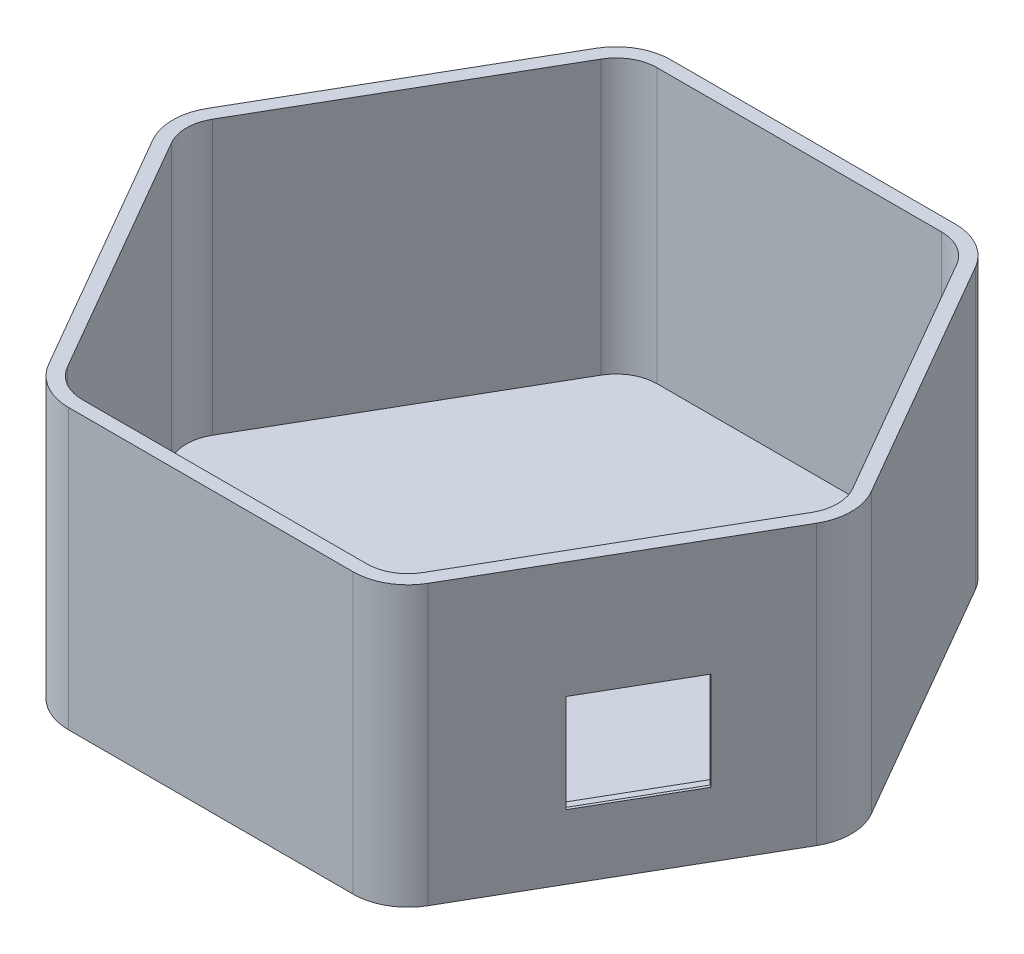
SolidWorks part; units mm, degrees
ref_plane "Front" through (0, 0, 0) normal (0, 0, 1) x (1, 0, 0)
ref_plane "Top" through (0, 0, 0) normal (0, 1, 0) x (1, 0, 0)
ref_plane "Right" through (0, 0, 0) normal (1, 0, 0) x (0, 0, -1)
sketch "Croquis1" plane through (0, 0, 0) normal (0, 1, 0) x (1, 0, 0)
  line L1 (-121.2436, -10) -> (-69.282, -100)
  line L2 (-51.9615, -110) -> (51.9615, -110)
  line L3 (69.282, -100) -> (121.2436, -10)
  line L4 (121.2436, 10) -> (69.282, 100)
  line L5 (51.9615, 110) -> (-51.9615, 110)
  line L6 (-69.282, 100) -> (-121.2436, 10)
  circle A0 centre (0, 0) radius 110 construction
  arc A1 (-69.282, 100) -> (-51.9615, 110) centre (-51.9615, 90) cw
  arc A2 (69.282, 100) -> (51.9615, 110) centre (51.9615, 90) ccw
  arc A3 (121.2436, -10) -> (121.2436, 10) centre (103.923, 0) ccw
  arc A4 (51.9615, -110) -> (69.282, -100) centre (51.9615, -90) ccw
  arc A5 (-69.282, -100) -> (-51.9615, -110) centre (-51.9615, -90) ccw
  arc A6 (-121.2436, -10) -> (-121.2436, 10) centre (-103.923, 0) cw
  dimension "D1" = 220
  dimension "D2" = 20
extrude "Saliente-Extruir1" add sketch "Croquis1" along normal blind 2
sketch "Croquis2" plane through (0, 2, 0) normal (0, 1, 0) x (1, 0, 0)
  line L6 (-64.9519, 97.5) -> (-116.9134, 7.5)
  line L7 (-116.9134, -7.5) -> (-64.9519, -97.5)
  line L8 (-51.9615, -105) -> (51.9615, -105)
  line L9 (64.9519, -97.5) -> (116.9134, -7.5)
  line L10 (116.9134, 7.5) -> (64.9519, 97.5)
  line L11 (51.9615, 105) -> (-51.9615, 105)
  line L12 (-69.282, 100) -> (-121.2436, 10)
  line L13 (-121.2436, -10) -> (-69.282, -100)
  line L14 (-51.9615, -110) -> (51.9615, -110)
  line L15 (69.282, -100) -> (121.2436, -10)
  line L16 (121.2436, 10) -> (69.282, 100)
  line L17 (51.9615, 110) -> (-51.9615, 110)
  line L18 (-69.282, 100) -> (-121.2436, 10)
  line L19 (-121.2436, -10) -> (-69.282, -100)
  line L20 (-51.9615, -110) -> (51.9615, -110)
  line L21 (69.282, -100) -> (121.2436, -10)
  line L22 (121.2436, 10) -> (69.282, 100)
  line L23 (51.9615, 110) -> (-51.9615, 110)
  arc A6 (-116.9134, 7.5) -> (-116.9134, -7.5) centre (-103.923, 0) ccw
  arc A7 (-64.9519, -97.5) -> (-51.9615, -105) centre (-51.9615, -90) ccw
  arc A8 (51.9615, -105) -> (64.9519, -97.5) centre (51.9615, -90) ccw
  arc A9 (116.9134, -7.5) -> (116.9134, 7.5) centre (103.923, 0) ccw
  arc A10 (64.9519, 97.5) -> (51.9615, 105) centre (51.9615, 90) ccw
  arc A11 (-51.9615, 105) -> (-64.9519, 97.5) centre (-51.9615, 90) ccw
  arc A12 (-51.9615, 110) -> (-69.282, 100) centre (-51.9615, 90) ccw
  arc A13 (-121.2436, 10) -> (-121.2436, -10) centre (-103.923, 0) ccw
  arc A14 (-69.282, -100) -> (-51.9615, -110) centre (-51.9615, -90) ccw
  arc A15 (51.9615, -110) -> (69.282, -100) centre (51.9615, -90) ccw
  arc A16 (121.2436, -10) -> (121.2436, 10) centre (103.923, 0) ccw
  arc A17 (69.282, 100) -> (51.9615, 110) centre (51.9615, 90) ccw
  arc A18 (-51.9615, 110) -> (-69.282, 100) centre (-51.9615, 90) ccw
  arc A19 (-121.2436, 10) -> (-121.2436, -10) centre (-103.923, 0) ccw
  arc A20 (-69.282, -100) -> (-51.9615, -110) centre (-51.9615, -90) ccw
  arc A21 (51.9615, -110) -> (69.282, -100) centre (51.9615, -90) ccw
  arc A22 (121.2436, -10) -> (121.2436, 10) centre (103.923, 0) ccw
  arc A23 (69.282, 100) -> (51.9615, 110) centre (51.9615, 90) ccw
  dimension "D1" = 0
  dimension "D2" = 5
extrude "Saliente-Extruir2" add sketch "Croquis2" along normal blind 100
sketch "Croquis3" plane through (90.9327, 0, 52.5) normal (-0.866, 0, -0.5) x (-0.5, 0, 0.866)
  line L1 (27.9238, 60.6352) -> (27.9238, 22.4352)
  line L2 (27.9238, 60.6352) -> (-30.7762, 60.6352)
  line L3 (-30.7762, 60.6352) -> (-30.7762, 22.4352)
  line L4 (27.9238, 22.4352) -> (-30.7762, 22.4352)
  line L5 (-23.7762, 59.4352) -> (15.0238, 59.4352)
  line L6 (-23.7762, 59.4352) -> (-23.7762, 23.6352)
  line L7 (-23.7762, 23.6352) -> (15.0238, 23.6352)
  line L8 (15.0238, 59.4352) -> (15.0238, 23.6352)
  circle A0 centre (24.9238, 57.6352) radius 1.5
  circle A1 centre (24.9238, 25.4352) radius 1.5
  circle A2 centre (-27.7762, 25.4352) radius 1.5
  circle A3 centre (-27.7762, 57.6352) radius 1.5
  dimension "D1" = 3
  dimension "D2" = 3
  dimension "D3" = 58.7
  dimension "D4" = 3
  dimension "D5" = 3
  dimension "D6" = 3
  dimension "D7" = 3
  dimension "D8" = 3
  dimension "D9" = 3
  dimension "D10" = 3
  dimension "D11" = 38.2
  dimension "D12" = 35.8
  dimension "D13" = 38.8
  dimension "D14" = 1.2
  dimension "D15" = 7
extrude "Cortar-Extruir1" cut sketch "Croquis3" against normal blind 1
sketch "Croquis4" plane through (90.9327, 0, 52.5) normal (-0.866, 0, -0.5) x (-0.5, 0, 0.866)
  line L4 (15.0238, 59.4352) -> (-23.7762, 59.4352)
  line L5 (-23.7762, 59.4352) -> (-23.7762, 23.6352)
  line L6 (-23.7762, 23.6352) -> (15.0238, 23.6352)
  line L7 (15.0238, 23.6352) -> (15.0238, 59.4352)
  line L8 (15.0238, 59.4352) -> (-23.7762, 59.4352)
  line L9 (-23.7762, 59.4352) -> (-23.7762, 23.6352)
  line L10 (-23.7762, 23.6352) -> (15.0238, 23.6352)
  line L11 (15.0238, 23.6352) -> (15.0238, 59.4352)
  dimension "D1" = 0
extrude "Cortar-Extruir2" cut sketch "Croquis4" against normal blind 12
sketch "Croquis5" plane through (91.7987, 0, 53) normal (-0.866, 0, -0.5) x (-0.5, 0, 0.866)
  line L4 (27.9238, 60.6352) -> (-30.7762, 60.6352)
  line L5 (-30.7762, 60.6352) -> (-30.7762, 22.4352)
  line L6 (-30.7762, 22.4352) -> (27.9238, 22.4352)
  line L7 (27.9238, 22.4352) -> (27.9238, 60.6352)
  line L8 (27.9238, 60.6352) -> (-30.7762, 60.6352)
  line L9 (-30.7762, 60.6352) -> (-30.7762, 22.4352)
  line L10 (-30.7762, 22.4352) -> (27.9238, 22.4352)
  line L11 (27.9238, 22.4352) -> (27.9238, 60.6352)
  circle A0 centre (24.9238, 25.4352) radius 1.5 construction
  circle A1 centre (24.9238, 57.6352) radius 1.5 construction
  circle A2 centre (-27.7762, 57.6352) radius 1.5 construction
  circle A3 centre (-27.7762, 25.4352) radius 1.5 construction
  circle A4 centre (24.9238, 25.4352) radius 1.5
  circle A5 centre (24.9238, 57.6352) radius 1.5
  circle A6 centre (-27.7762, 57.6352) radius 1.5
  circle A7 centre (-27.7762, 25.4352) radius 1.5
  dimension "D1" = 0
extrude "Cortar-Extruir3" cut sketch "Croquis5" against normal blind 3
sketch "Croquis6" plane through (94.3968, 0, 54.5) normal (-0.866, 0, -0.5) x (-0.5, 0, 0.866)
  line L0 (-28.444, 58.9783) -> (-27.1084, 56.292) construction
  line L1 (-30.7762, 60.6352) -> (-25.7762, 60.6352)
  line L2 (-30.7762, 60.6352) -> (-30.7762, 55.6352)
  line L3 (-30.7762, 55.6352) -> (-26.7762, 55.6352)
  line L4 (-25.7762, 60.6352) -> (-25.7762, 56.6352)
  line L5 (-30.7762, 22.4352) -> (-25.7762, 22.4352)
  line L6 (-30.7762, 22.4352) -> (-30.7762, 27.4352)
  line L7 (-30.7762, 27.4352) -> (-26.7762, 27.4352)
  line L8 (-25.7762, 22.4352) -> (-25.7762, 26.4352)
  line L9 (27.9238, 22.4352) -> (22.9238, 22.4352)
  line L10 (27.9238, 22.4352) -> (27.9238, 27.4352)
  line L11 (27.9238, 27.4352) -> (23.9238, 27.4352)
  line L12 (22.9238, 22.4352) -> (22.9238, 26.4352)
  line L13 (27.9238, 60.6352) -> (22.9238, 60.6352)
  line L14 (27.9238, 60.6352) -> (27.9238, 55.6352)
  line L15 (27.9238, 55.6352) -> (23.9238, 55.6352)
  line L16 (22.9238, 60.6352) -> (22.9238, 56.6352)
  circle A0 centre (-27.7762, 57.6352) radius 1.5 construction
  circle A1 centre (-27.7762, 57.6352) radius 1.5 construction
  circle A2 centre (-27.7762, 25.4352) radius 1
  circle A3 centre (-27.7762, 57.6352) radius 1
  circle A4 centre (24.9238, 57.6352) radius 1
  circle A5 centre (24.9238, 25.4352) radius 1
  arc A6 (-26.7762, 55.6352) -> (-25.7762, 56.6352) centre (-26.7762, 56.6352) ccw
  arc A7 (-25.7762, 26.4352) -> (-26.7762, 27.4352) centre (-26.7762, 26.4352) ccw
  arc A8 (22.9238, 26.4352) -> (23.9238, 27.4352) centre (23.9238, 26.4352) cw
  arc A9 (23.9238, 55.6352) -> (22.9238, 56.6352) centre (23.9238, 56.6352) cw
  point P39 (-25.7762, 55.6352)
  dimension "D1" = 5
  dimension "D9" = 1
  dimension "D2" = 5
  dimension "D3" = 5
  dimension "D4" = 5
  dimension "D5" = 5
  dimension "D6" = 5
  dimension "D7" = 5
  dimension "D8" = 5
extrude "Saliente-Extruir3" add sketch "Croquis6" along normal blind 3.4
sketch "Croquis8" plane through (90.9327, 0, 52.5) normal (-0.866, 0, -0.5) x (-0.5, 0, 0.866)
  circle A0 centre (-27.7762, 57.6352) radius 1
  circle A1 centre (-27.7762, 25.4352) radius 1
  circle A2 centre (24.9238, 25.4352) radius 1
  circle A3 centre (24.9238, 57.6352) radius 1
extrude "Cortar-Extruir5" cut sketch "Croquis8" against normal up to surface (4 mm away) up to face at (96.5849, 41.5352, 50.7101)
sketch "Croquis10" plane through (90.9327, 0, 52.5) normal (-0.866, 0, -0.5) x (-0.5, 0, 0.866)
  line L0 (27.9238, 60.6352) -> (-30.7762, 60.6352) construction
  line L1 (27.9238, 60.6352) -> (-30.7762, 60.6352)
  line L2 (-30.7762, 60.6352) -> (-30.7762, 22.4352) construction
  line L3 (-30.7762, 55.6352) -> (-30.7762, 27.4352) construction
  line L4 (-30.7762, 60.6352) -> (-30.7762, 22.4352)
  line L5 (-30.7762, 55.6352) -> (-30.7762, 27.4352)
  line L6 (-30.7762, 22.4352) -> (27.9238, 22.4352) construction
  line L7 (-30.7762, 22.4352) -> (27.9238, 22.4352)
  line L8 (27.9238, 22.4352) -> (27.9238, 60.6352) construction
  line L9 (27.9238, 22.4352) -> (27.9238, 60.6352)
  line M1 (-30.7762, 60.6352) -> (27.9238, 60.6352)
  line M2 (27.9238, 60.6352) -> (27.9238, 22.4352)
  line M3 (27.9238, 22.4352) -> (-30.7762, 22.4352)
  line M4 (-30.7762, 22.4352) -> (-30.7762, 60.6352)
extrude "Cortar-Extruir6" cut sketch "Croquis10" against normal up to surface (0.6 mm away) contours L4 M1 M4 M3 M2 region at (91.6458, 41.5352, 51.2649) up to face at (104.5904, 57.6352, 30.0442)
